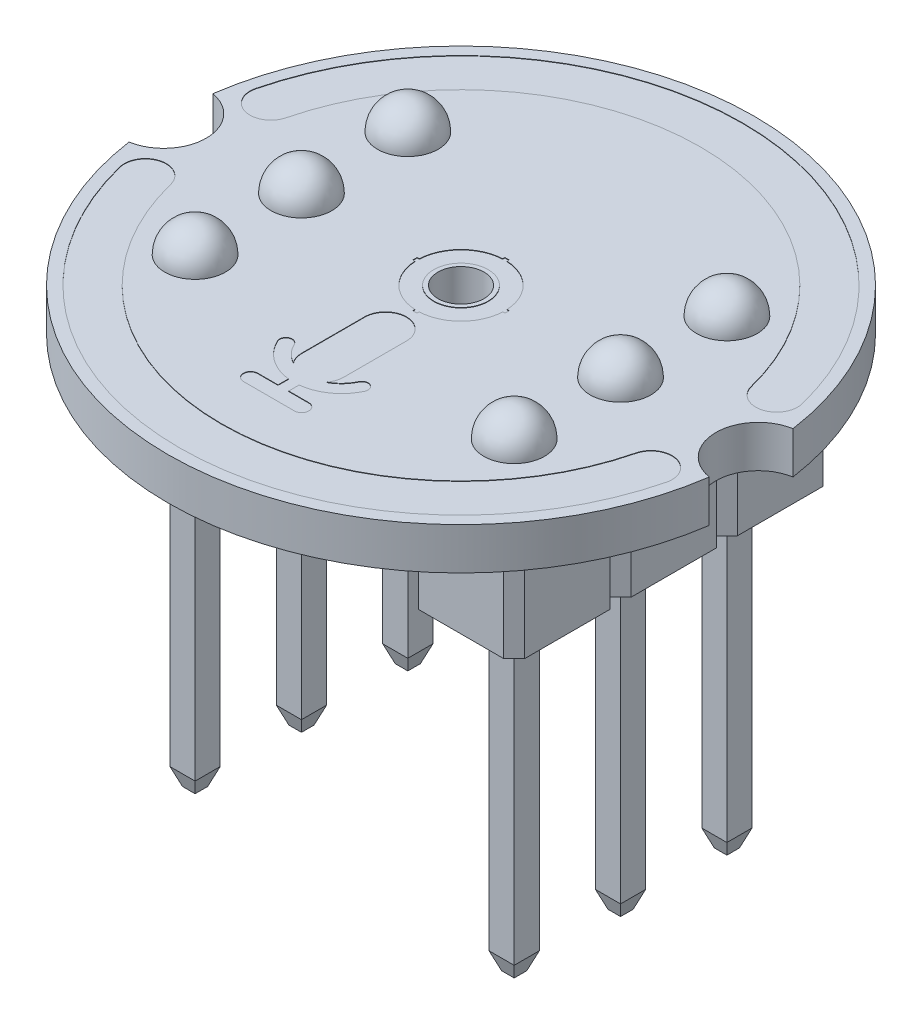
SolidWorks part; units mm, degrees
ref_plane "Спереди" through (0, 0, 0) normal (0, 0, 1) x (1, 0, 0)
ref_plane "Сверху" through (0, 0, 0) normal (0, 1, 0) x (1, 0, 0)
ref_plane "Справа" through (0, 0, 0) normal (1, 0, 0) x (0, 0, -1)
sketch "Эскиз1" plane through (0, 0, 0) normal (0, 1, 0) x (1, 0, 0)
  line L0 (-7.1, 0) -> (7.1, 0) construction
  arc A0 (-6.9282, -1) -> (6.9282, -1) centre (0, 0) ccw
  arc A3 (-6.9282, -1) -> (-6.9282, 1) centre (-7.1, 0) ccw
  arc A4 (6.9282, 1) -> (6.9282, -1) centre (7.1, 0) ccw
  arc A5 (6.9282, 1) -> (-6.9282, 1) centre (0, 0) ccw
  circle A6 centre (0, 0) radius 0.55
  point P7 (0, 0)
  point P8 (-6.9282, -1)
  point P9 (-6.9282, 1)
  dimension "D1" = 14
  dimension "D2" = 2
  dimension "D4" = 1.1
  dimension "D3" = 7.1
extrude "Бобышка-Вытянуть1" add sketch "Эскиз1" along normal blind 1
sketch "Эскиз2" plane through (0, 1, 0) normal (0, 1, 0) x (1, 0, 0)
  line L0 (-6.0854, 0) -> (6.0854, 0) construction
  line L1 (-6.0387, 1.5) -> (6.0387, 1.5) construction
  line L3 (-0.05, 1.1) -> (0.05, 1.1)
  line L4 (-0.05, 1.1) -> (-0.05, 1.0488)
  line L5 (-0.05, -1.1) -> (0.05, -1.1)
  line L6 (0.05, 1.1) -> (0.05, 1.0488)
  line L7 (-0.05, 1.1) -> (0.05, -1.1) construction
  line L8 (-0.05, -1.1) -> (0.05, 1.1) construction
  line L9 (-1.1, 0.05) -> (-1.0488, 0.05)
  line L10 (-1.1, 0.05) -> (-1.1, -0.05)
  line L11 (-1.1, -0.05) -> (-1.0488, -0.05)
  line L12 (1.1, 0.05) -> (1.1, -0.05)
  line L13 (-1.1, 0.05) -> (1.1, -0.05) construction
  line L14 (-1.1, -0.05) -> (1.1, 0.05) construction
  line L15 (-0.0023, -0.05) -> (0.0023, -0.05)
  line L16 (1.0488, -0.05) -> (1.1, -0.05)
  line L17 (0.05, -1.0488) -> (0.05, -1.1)
  line L18 (-0.05, -1.0488) -> (-0.05, -1.1)
  line L19 (-0.05, 0.0023) -> (-0.05, -0.0023)
  line L20 (0.05, 0.0023) -> (0.05, -0.0023)
  line L21 (1.0488, 0.05) -> (1.1, 0.05)
  line L22 (-0.0023, 0.05) -> (0.0023, 0.05)
  arc A0 (-6.0387, 1.5) -> (6.0387, 1.5) centre (0, 0) cw construction
  arc A1 (6.524, 1.6205) -> (-6.524, 1.6205) centre (0, 0) ccw
  arc A2 (5.5535, 1.3795) -> (-5.5535, 1.3795) centre (0, 0) ccw
  arc A3 (5.5535, 1.3795) -> (6.524, 1.6205) centre (6.0387, 1.5) ccw
  arc A4 (-6.524, 1.6205) -> (-5.5535, 1.3795) centre (-6.0387, 1.5) ccw
  arc A5 (-6.9282, -1) -> (-6.9282, 1) centre (-7.1, 0) ccw construction
  arc A6 (6.9282, 1) -> (6.9282, -1) centre (7.1, 0) ccw construction
  arc A7 (-6.0387, -1.5) -> (6.0387, -1.5) centre (0, 0) ccw construction
  arc A8 (6.524, -1.6205) -> (-6.524, -1.6205) centre (0, 0) cw
  arc A9 (5.5535, -1.3795) -> (-5.5535, -1.3795) centre (0, 0) cw
  arc A10 (5.5535, -1.3795) -> (6.524, -1.6205) centre (6.0387, -1.5) cw
  arc A11 (-6.524, -1.6205) -> (-5.5535, -1.3795) centre (-6.0387, -1.5) cw
  circle A12 centre (0, 0) radius 0.65
  arc A13 (-1.0488, -0.05) -> (-0.05, -1.0488) centre (0, 0) ccw
  circle A14 centre (0, 0) radius 0.55 construction
  arc A15 (-0.05, 1.0488) -> (-1.0488, 0.05) centre (0, 0) ccw
  arc A16 (1.0488, 0.05) -> (0.05, 1.0488) centre (0, 0) ccw
  arc A17 (0.05, -1.0488) -> (1.0488, -0.05) centre (0, 0) ccw
  point P4 (0, 6.2222)
  point P17 (0, 1.5)
  point P24 (0, -6.2222)
  dimension "D1" = 0.5
  dimension "D3" = 0.1
  dimension "D4" = 0.4
  dimension "D6" = 1.1
  dimension "D2" = 3
  dimension "D5" = 0.1
extrude "Вырез-Вытянуть1" cut sketch "Эскиз2" against normal blind 0.01 contours A11 A8 A10 A9 | A1 A4 A2 A3 | L17 A17 L16 L12 L21 A16 L6 L3 L4 A15 L9 L10 L11 A13 L18 L5 A12 region at (0, 1, -1.0689) region at (6.1248, 1, -1.1533) region at (0, 1, 6.5795)
sketch "Эскиз3" plane through (0, 1, 0) normal (0, 1, 0) x (1, 0, 0)
  line L0 (-3.81, 2.54) -> (-3.81, 0) construction
  line L1 (-3.81, 0) -> (-3.81, -2.54) construction
  line L2 (-3.81, 0) -> (3.81, 0) construction
  line L3 (3.81, 2.54) -> (3.81, 0) construction
  line L4 (3.81, 0) -> (3.81, -2.54) construction
  circle A0 centre (-3.81, 2.54) radius 0.725
  circle A1 centre (-3.81, 0) radius 0.725
  circle A2 centre (-3.81, -2.54) radius 0.725
  circle A3 centre (3.81, 2.54) radius 0.725
  circle A4 centre (3.81, 0) radius 0.725
  circle A5 centre (3.81, -2.54) radius 0.725
  point P12 (0, 0)
  dimension "D1" = 2.54
  dimension "D3" = 1.45
  dimension "D2" = 7.62
extrude "Бобышка-Вытянуть2" add sketch "Эскиз3" along normal blind 0.725
fillet "Скругление1" radius 0.725 6 edges at (3.81, 1.725, -1.815) (3.81, 1.725, 0.725) (3.81, 1.725, 3.265) (-3.81, 1.725, -1.815) (-3.81, 1.725, 0.725) (-3.81, 1.725, 3.265)
sketch "Эскиз4" plane through (0, 1, 0) normal (0, 1, 0) x (1, 0, 0)
  line L0 (0, -1.8016) -> (0, -3.3016) construction
  line L1 (0.5, -1.8016) -> (0.5, -3.3016)
  line L2 (-0.5, -1.8016) -> (-0.5, -3.3016)
  line L3 (-0.9063, -3.2742) -> (0.9063, -3.2742) construction
  line L4 (-0.9063, -3.2742) -> (0, -2.8516) construction
  line L5 (0, -2.8516) -> (0.9063, -3.2742) construction
  line L6 (0.1283, -4.243) -> (0.6091, -4.243)
  line L7 (-0.6091, -4.243) -> (-0.1258, -4.243)
  line L8 (-0.6091, -4.5865) -> (0.6091, -4.5865)
  line L11 (-0.1258, -3.9947) -> (-0.1258, -4.243)
  line L13 (0.1283, -3.9944) -> (0.1283, -4.243)
  arc A2 (0.5, -1.8016) -> (-0.5, -1.8016) centre (0, -1.8016) ccw
  arc A3 (-0.5, -3.3016) -> (-0.4, -3.6016) centre (0, -3.3016) ccw
  arc A4 (0.9063, -3.2742) -> (-0.9063, -3.2742) centre (0, -2.8516) cw construction
  arc A5 (-1.0423, -3.3376) -> (-0.1258, -3.9947) centre (0, -2.8516) ccw
  arc A6 (-0.7704, -3.2108) -> (-0.4, -3.6016) centre (0, -2.8516) ccw
  arc A7 (-0.7704, -3.2108) -> (-1.0423, -3.3376) centre (-0.9063, -3.2742) ccw
  arc A8 (1.0423, -3.3376) -> (0.7704, -3.2108) centre (0.9063, -3.2742) ccw
  arc A9 (-0.6091, -4.243) -> (-0.6091, -4.5865) centre (-0.6091, -4.4148) ccw
  arc A10 (0.6091, -4.5865) -> (0.6091, -4.243) centre (0.6091, -4.4148) ccw
  arc A11 (0.1283, -3.9944) -> (1.0423, -3.3376) centre (0, -2.8516) ccw
  arc A12 (0.4, -3.6016) -> (0.5, -3.3016) centre (0, -3.3016) ccw
  arc A13 (0.4, -3.6016) -> (0.7704, -3.2108) centre (0, -2.8516) ccw
  point P2 (0, -2.5516)
  point P11 (0, -3.8516)
  point P16 (0, -4.4148)
  dimension "D1" = 0.5
  dimension "D3" = 0.15
  dimension "D4" = 1
  dimension "D2" = 1.5
  dimension "D5" = 130
  dimension "D6" = 1.3
extrude "Вырез-Вытянуть2" cut sketch "Эскиз4" against normal blind 0.01
sketch "Эскиз5" plane through (0, 0, 0) normal (0, -1, 0) x (1, 0, 0)
  line L0 (-5.08, 3.56) -> (-4.83, 3.81)
  line L1 (-4.83, 3.81) -> (-2.79, 3.81)
  line L2 (-5.08, 3.56) -> (-5.08, 1.52)
  line L3 (-4.83, 1.27) -> (-2.79, 1.27)
  line L4 (-2.54, 3.56) -> (-2.54, 1.52)
  line L5 (-2.79, 3.81) -> (-2.54, 3.56)
  line L6 (-2.79, 1.27) -> (-2.54, 1.52)
  line L7 (-5.08, 1.52) -> (-4.83, 1.27)
  line L8 (2.54, 3.56) -> (2.54, 1.52)
  line L9 (2.54, 1.52) -> (2.79, 1.27)
  line L10 (2.54, 3.56) -> (2.79, 3.81)
  line L11 (2.79, 3.81) -> (4.83, 3.81)
  line L12 (4.83, 3.81) -> (5.08, 3.56)
  line L13 (5.08, 3.56) -> (5.08, 1.52)
  line L14 (4.83, 1.27) -> (5.08, 1.52)
  line L15 (2.79, 1.27) -> (4.83, 1.27)
  line L16 (2.54, 1.02) -> (2.54, -1.02)
  line L17 (2.54, -1.02) -> (2.79, -1.27)
  line L18 (2.54, 1.02) -> (2.79, 1.27)
  line L19 (2.79, 1.27) -> (4.83, 1.27)
  line L20 (4.83, 1.27) -> (5.08, 1.02)
  line L21 (5.08, 1.02) -> (5.08, -1.02)
  line L22 (4.83, -1.27) -> (5.08, -1.02)
  line L23 (2.79, -1.27) -> (4.83, -1.27)
  line L24 (2.54, -1.52) -> (2.54, -3.56)
  line L25 (2.54, -3.56) -> (2.79, -3.81)
  line L26 (2.54, -1.52) -> (2.79, -1.27)
  line L27 (2.79, -1.27) -> (4.83, -1.27)
  line L28 (4.83, -1.27) -> (5.08, -1.52)
  line L29 (5.08, -1.52) -> (5.08, -3.56)
  line L30 (4.83, -3.81) -> (5.08, -3.56)
  line L31 (2.79, -3.81) -> (4.83, -3.81)
  line L32 (-5.08, 1.02) -> (-5.08, -1.02)
  line L33 (-5.08, -1.02) -> (-4.83, -1.27)
  line L34 (-5.08, 1.02) -> (-4.83, 1.27)
  line L35 (-4.83, 1.27) -> (-2.79, 1.27)
  line L36 (-2.79, 1.27) -> (-2.54, 1.02)
  line L37 (-2.54, 1.02) -> (-2.54, -1.02)
  line L38 (-2.79, -1.27) -> (-2.54, -1.02)
  line L39 (-4.83, -1.27) -> (-2.79, -1.27)
  line L40 (-5.08, -1.52) -> (-5.08, -3.56)
  line L41 (-5.08, -3.56) -> (-4.83, -3.81)
  line L42 (-5.08, -1.52) -> (-4.83, -1.27)
  line L43 (-4.83, -1.27) -> (-2.79, -1.27)
  line L44 (-2.79, -1.27) -> (-2.54, -1.52)
  line L45 (-2.54, -1.52) -> (-2.54, -3.56)
  line L46 (-2.79, -3.81) -> (-2.54, -3.56)
  line L47 (-4.83, -3.81) -> (-2.79, -3.81)
  line L48 (-3.81, 0) -> (3.81, 0) construction
  point P0 (-5.08, 3.81)
  point P1 (-2.54, 1.27)
  point P2 (-5.08, 1.27)
  point P3 (-2.54, 3.81)
  point P12 (-3.81, 2.54)
  point P14 (-3.81, 3.81)
  point P15 (-5.08, 2.54)
  point P25 (3.81, 2.54)
  point P34 (3.81, 0)
  point P43 (3.81, -2.54)
  point P52 (-3.81, 0)
  point P61 (-3.81, -2.54)
  point P62 (0, 0)
  dimension "D1" = 2.54
  dimension "D2" = 2
  dimension "D8" = 2.54
  dimension "D9" = 7.62
  dimension "D3" = 3
extrude "Бобышка-Вытянуть3" add sketch "Эскиз5" along normal blind 2.4 contours L2 L7 L3 L6 L4 L5 L1 L0 | L33 L39 L38 L37 L36 L3 L34 L32 | L41 L47 L46 L45 L44 L39 L42 L40 | L9 L15 L14 L13 L12 L11 L10 L8 | L17 L23 L22 L21 L20 L15 L18 L16 | L25 L31 L30 L29 L28 L23 L26 L24 region at (-3.81, 0, 2.54) region at (-3.81, 0, 0) region at (-3.81, 0, -2.54) region at (3.81, 0, 2.54) region at (3.81, 0, 0) region at (3.81, 0, -2.54)
sketch "Эскиз6" plane through (0, 0, 3.81) normal (0, 0, 1) x (1, 0, 0)
  line L0 (-6.9282, 0) -> (6.9282, 0) construction
  line L1 (-4.73, 0) -> (-2.89, 0)
  line L2 (-4.73, 0) -> (-4.73, -0.2)
  line L3 (-4.73, -0.2) -> (-2.89, -0.2)
  line L4 (-2.89, 0) -> (-2.89, -0.2)
  line L5 (2.79, 0) -> (4.83, 0) construction
  line L6 (2.89, 0) -> (4.73, 0)
  line L7 (2.89, 0) -> (2.89, -0.2)
  line L8 (2.89, -0.2) -> (4.73, -0.2)
  line L9 (4.73, 0) -> (4.73, -0.2)
  line L10 (-4.83, -2.4) -> (-2.79, -2.4) construction
  line L11 (2.79, -2.4) -> (4.83, -2.4) construction
  line L12 (-4.83, -2.4) -> (-4.83, 0) construction
  point P14 (-3.81, -2.4)
  point P15 (-3.81, -0.2)
  point P18 (3.81, -2.4)
  point P19 (3.81, -0.2)
  dimension "D1" = 0.1
  dimension "D2" = 0.2
extrude "Вырез-Вытянуть3" cut sketch "Эскиз6" against normal through all
sketch "Эскиз7" plane through (0, -2.4, 0) normal (0, -1, 0) x (1, 0, 0)
  line L0 (-5.08, 3.56) -> (-5.08, 1.52) construction
  line L1 (-4.11, 2.84) -> (-3.51, 2.84)
  line L2 (-4.11, 2.84) -> (-4.11, 2.24)
  line L3 (-4.11, 2.24) -> (-3.51, 2.24)
  line L4 (-3.51, 2.84) -> (-3.51, 2.24)
  line L5 (-4.11, 2.84) -> (-3.51, 2.24) construction
  line L6 (-4.11, 2.24) -> (-3.51, 2.84) construction
  line L7 (-4.83, 3.81) -> (-2.79, 3.81) construction
  line L8 (3.51, 2.84) -> (3.51, 2.24)
  line L9 (3.51, 2.84) -> (4.11, 2.84)
  line L10 (4.11, 2.84) -> (4.11, 2.24)
  line L11 (3.51, 2.24) -> (4.11, 2.24)
  line L12 (3.51, 0.3) -> (3.51, -0.3)
  line L13 (3.51, 0.3) -> (4.11, 0.3)
  line L14 (4.11, 0.3) -> (4.11, -0.3)
  line L15 (3.51, -0.3) -> (4.11, -0.3)
  line L16 (3.51, -2.24) -> (3.51, -2.84)
  line L17 (3.51, -2.24) -> (4.11, -2.24)
  line L18 (4.11, -2.24) -> (4.11, -2.84)
  line L19 (3.51, -2.84) -> (4.11, -2.84)
  line L20 (-4.11, 0.3) -> (-4.11, -0.3)
  line L21 (-4.11, 0.3) -> (-3.51, 0.3)
  line L22 (-3.51, 0.3) -> (-3.51, -0.3)
  line L23 (-4.11, -0.3) -> (-3.51, -0.3)
  line L24 (-4.11, -2.24) -> (-4.11, -2.84)
  line L25 (-4.11, -2.24) -> (-3.51, -2.24)
  line L26 (-3.51, -2.24) -> (-3.51, -2.84)
  line L27 (-4.11, -2.84) -> (-3.51, -2.84)
  point P0 (-3.81, 2.54)
  point P7 (-5.08, 2.54)
  point P10 (-3.81, 3.81)
  dimension "D1" = 0.6
  dimension "D2" = 2
  dimension "D4" = 2.54
  dimension "D5" = 7.62
  dimension "D3" = 3
extrude "Бобышка-Вытянуть4" add sketch "Эскиз7" along normal offset from surface 11 and the other way up to surface (2.4 mm away) up to face at (0.0003, 1, 3.5658) other way up to face at (-4.9383, 0, 0)
chamfer "Фаска1" distance 0.15 angle 70 24 edges at (3.81, -10, -2.84) (3.51, -10, -2.54) (3.81, -10, -2.24) (4.11, -10, -2.54) (3.81, -10, -0.3) (3.51, -10, 0) (3.81, -10, 0.3) (4.11, -10, 0) (3.81, -10, 2.24) (3.51, -10, 2.54) (3.81, -10, 2.84) (4.11, -10, 2.54) (-3.81, -10, -2.84) (-4.11, -10, -2.54) (-3.81, -10, -2.24) (-3.51, -10, -2.54) (-3.81, -10, -0.3) (-4.11, -10, 0) (-3.81, -10, 0.3) (-3.51, -10, 0) (-3.51, -10, 2.54) (-3.81, -10, 2.24) (-4.11, -10, 2.54) (-3.81, -10, 2.84) first distance on face at (3.81, -10, -2.54) first distance on face at (3.81, -10, 0) first distance on face at (3.81, -10, 2.54) first distance on face at (-3.81, -10, -2.54) first distance on face at (-3.81, -10, 0) first distance on face at (-3.81, -10, 2.54)
sketch "Эскиз9" plane through (0, 0, 0) normal (0, -1, 0) x (1, 0, 0)
  line L1 (-1.875, 3.8) -> (1.875, 3.8)
  line L2 (-1.875, 3.8) -> (-1.875, -0.95)
  line L3 (-1.875, -0.95) -> (1.875, -0.95)
  line L4 (1.875, 3.8) -> (1.875, -0.95)
  line L5 (-1.875, 3.8) -> (1.875, -0.95) construction
  line L6 (-1.875, -0.95) -> (1.875, 3.8) construction
  arc A0 (6.9282, 1) -> (-6.9282, 1) centre (0, 0) ccw construction
  point P0 (0, 1.425)
  point P8 (0, 7)
  dimension "D1" = 3.75
  dimension "D2" = 4.75
  dimension "D3" = 3.2
extrude "Бобышка-Вытянуть5" add sketch "Эскиз9" along normal blind 0.2
fillet "Скругление2" radius 0.2 4 edges at (-1.875, -0.1, 3.8) (1.875, -0.1, 3.8) (-1.875, -0.1, -0.95) (1.875, -0.1, -0.95)
sketch "Эскиз11" plane through (0, -0.2, 0) normal (0, -1, 0) x (1, 0, 0)
  line L0 (-1.875, 3.6) -> (-1.875, -0.75) construction
  line L1 (-1.475, 3.4) -> (1.475, 3.4)
  line L2 (-1.475, 3.4) -> (-1.475, -0.55)
  line L3 (-1.475, -0.55) -> (1.475, -0.55)
  line L4 (1.475, 3.4) -> (1.475, -0.55)
  line L5 (-1.475, 3.4) -> (1.475, -0.55) construction
  line L6 (-1.475, -0.55) -> (1.475, 3.4) construction
  line L7 (0, 3.4) -> (0, 3.8) construction
  line L8 (1.675, 3.8) -> (-1.675, 3.8) construction
  line L9 (1.475, 1.425) -> (1.875, 1.425) construction
  line L10 (1.875, -0.75) -> (1.875, 3.6) construction
  point P0 (0, 1.425)
  point P7 (-1.875, 1.425)
  dimension "D1" = 0.4
extrude "Бобышка-Вытянуть6" add sketch "Эскиз11" along normal blind 0.3
fillet "Скругление3" radius 0.4 4 edges at (-1.475, -0.35, 3.4) (1.475, -0.35, 3.4) (-1.475, -0.35, -0.55) (1.475, -0.35, -0.55)
sketch "Эскиз12" plane through (0, 0, 0) normal (0, -1, 0) x (1, 0, 0)
  line L1 (-0.9, -2.6822) -> (0.9, -2.6822)
  line L2 (-0.9, -2.6822) -> (-0.9, -3.4822)
  line L3 (-0.9, -3.4822) -> (0.9, -3.4822)
  line L4 (0.9, -2.6822) -> (0.9, -3.4822)
  line L5 (-0.9, -2.6822) -> (0.9, -3.4822) construction
  line L6 (-0.9, -3.4822) -> (0.9, -2.6822) construction
  line L7 (-0.9, -3.9) -> (0.9, -3.9)
  line L8 (-0.9, -3.9) -> (-0.9, -4.7)
  line L9 (-0.9, -4.7) -> (0.9, -4.7)
  line L10 (0.9, -3.9) -> (0.9, -4.7)
  line L11 (-0.9, -3.9) -> (0.9, -4.7) construction
  line L12 (-0.9, -4.7) -> (0.9, -3.9) construction
  arc A0 (-6.9282, -1) -> (6.9282, -1) centre (0, 0) ccw construction
  point P0 (0, -3.0822)
  point P5 (0, -4.3)
  point P10 (0, -7)
  dimension "D1" = 0.8
  dimension "D2" = 1.8
  dimension "D3" = 2.3
extrude "Бобышка-Вытянуть7" add sketch "Эскиз12" along normal blind 0.6
